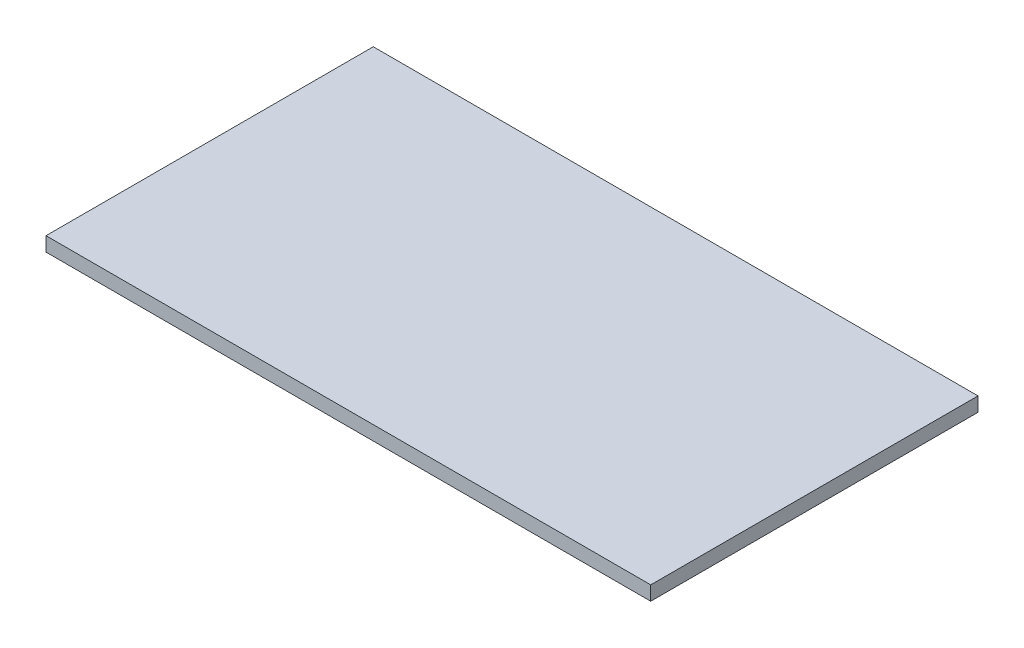
SolidWorks part; units mm, degrees
ref_plane "Front" through (0, 0, 0) normal (0, 0, 1) x (1, 0, 0)
ref_plane "Top" through (0, 0, 0) normal (0, 1, 0) x (1, 0, 0)
ref_plane "Right" through (0, 0, 0) normal (1, 0, 0) x (0, 0, -1)
sketch "草图1" plane through (0, 0, 0) normal (0, 1, 0) x (1, 0, 0)
  line L1 (-42.5, -23) -> (42.5, -23)
  line L2 (-42.5, -23) -> (-42.5, 23)
  line L3 (-42.5, 23) -> (42.5, 23)
  line L4 (42.5, -23) -> (42.5, 23)
  line L5 (-42.5, -23) -> (42.5, 23) construction
  line L6 (-42.5, 23) -> (42.5, -23) construction
  point P0 (0, 0)
  dimension "D1" = 85
  dimension "D2" = 46
extrude "凸台-拉伸1" add sketch "草图1" along normal blind 2
